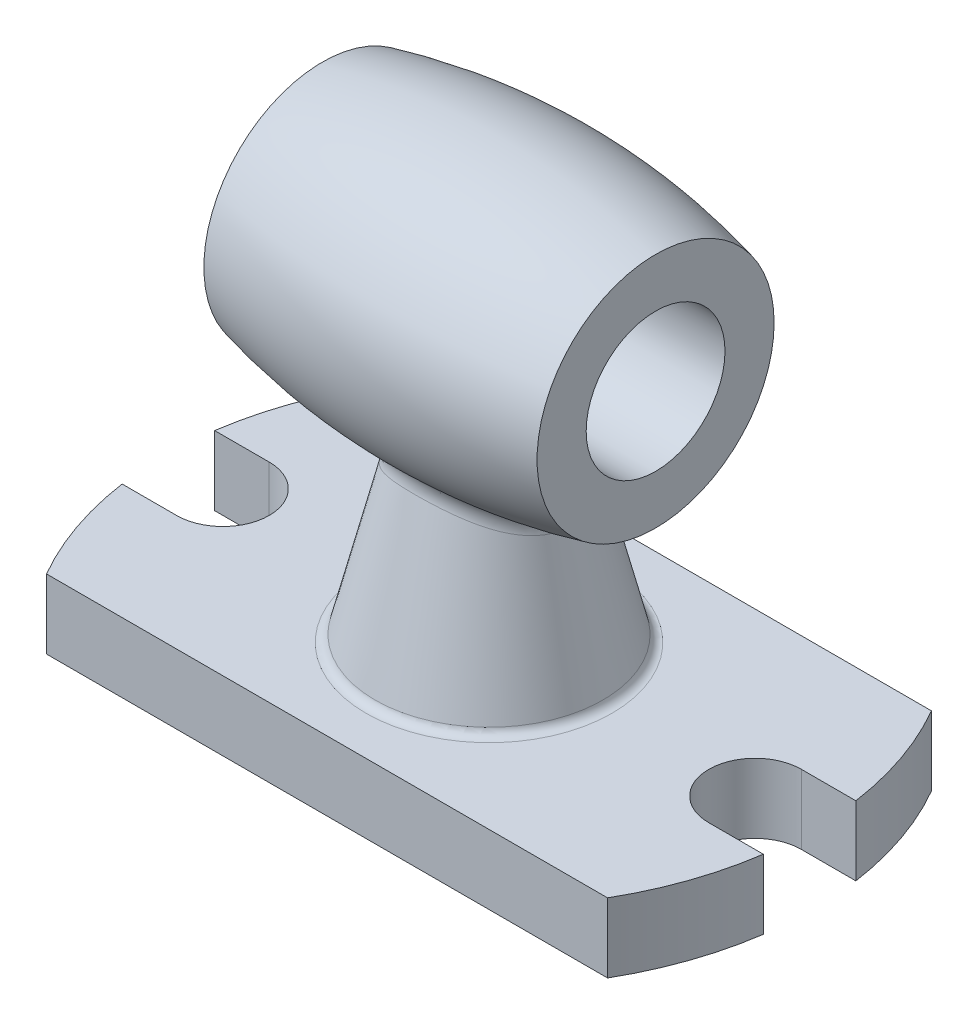
SolidWorks part; units mm, degrees
material "Plain Carbon Steel"
ref_plane "Front Plane" through (0, 0, 0) normal (0, 0, 1) x (1, 0, 0)
ref_plane "Top Plane" through (0, 0, 0) normal (0, 1, 0) x (1, 0, 0)
ref_plane "Right Plane" through (0, 0, 0) normal (1, 0, 0) x (0, 0, -1)
sketch "Sketch1" plane through (0, 0, 0) normal (0, 1, 0) x (1, 0, 0)
  line L0 (9.1225, -9.257) -> (9.1225, 60.743) construction
  line L5 (-48.3775, 60.743) -> (66.6225, 60.743)
  line L7 (-48.3775, -9.257) -> (66.6225, -9.257)
  line L9 (-48.3775, 25.743) -> (66.6225, 25.743) construction
  line L10 (66.6225, 60.743) -> (69.7443, 60.743)
  line L11 (66.6225, -9.257) -> (69.7443, -9.257)
  line L12 (-48.3775, 60.743) -> (-51.4993, 60.743)
  line L13 (-48.3775, -9.257) -> (-51.4993, -9.257)
  line L16 (-48.3775, 60.743) -> (-48.3775, -9.257) construction
  line L17 (66.6225, 60.743) -> (66.6225, -9.257) construction
  line L18 (-48.3775, 35.743) -> (-60.1596, 35.743)
  line L19 (-48.3775, 15.743) -> (-60.1596, 15.743)
  line L20 (66.6225, 35.743) -> (78.4045, 35.743)
  line L21 (66.6225, 15.743) -> (78.4045, 15.743)
  arc A0 (-51.4993, 60.743) -> (-60.1596, 35.743) centre (9.1225, 25.743) ccw
  arc A1 (69.7443, -9.257) -> (78.4045, 15.743) centre (9.1225, 25.743) ccw
  arc A2 (-48.3775, 15.743) -> (-48.3775, 35.743) centre (-48.3775, 25.743) ccw
  arc A3 (66.6225, 35.743) -> (66.6225, 15.743) centre (66.6225, 25.743) ccw
  arc A4 (78.4045, 35.743) -> (69.7443, 60.743) centre (9.1225, 25.743) ccw
  arc A5 (-60.1596, 15.743) -> (-51.4993, -9.257) centre (9.1225, 25.743) ccw
  dimension "D3" = 70
  dimension "D4" = 20
  dimension "D5" = 20
  dimension "D1" = 115
  dimension "D2" = 70
extrude "Boss-Extrude1" add sketch "Sketch1" along normal blind 15
ref_plane "Plane1" through (9.1225, 0, 0) normal (-1, 0, 0) x (0, 0, 1)
sketch "Sketch2" plane through (9.1225, 0, 0) normal (-1, 0, 0) x (0, 0, 1)
  line L0 (-25.743, 80) -> (-25.743, 15)
  line L1 (-15.743, 15) -> (-35.743, 15) construction
  line L2 (-50.743, 15) -> (-34.5367, 80)
  line L7 (-25.743, 15) -> (-50.743, 15)
  line L12 (-34.5367, 80) -> (-25.743, 80)
  dimension "D1" = 14
  dimension "D3" = 25
  dimension "D4" = 65
revolve "Revolve1" add sketch "Sketch2" angle 360 about L0
ref_plane "Plane2" through (0, 0, -25.743) normal (0, 0, 1) x (1, 0, 0)
sketch "Sketch6" plane through (0, 0, -25.743) normal (0, 0, 1) x (1, 0, 0)
  line L0 (-36.7283, 110) -> (-26.8775, 110) construction
  line L1 (-51.4993, 0) -> (69.7443, 0) construction
  line L2 (45.1225, 80) -> (60.6354, 80) construction
  line L3 (-41.3442, 95) -> (-26.8775, 95) construction
  line L4 (-60.1596, 15) -> (-60.1596, 65) construction
  line L5 (78.4045, 15) -> (78.4045, 83.7106) construction
  line L6 (-60.1596, 50) -> (-26.8775, 50) construction
  line L7 (9.1225, 50) -> (9.1225, 110) construction
  line L8 (9.1225, 50) -> (9.1225, -40) construction
  line L9 (45.1225, 80) -> (-26.8775, 80)
  line L10 (-43.3136, 65) -> (-26.8775, 65) construction
  line L11 (-26.8775, 119.2378) -> (-26.8775, 110) construction
  line L12 (45.1225, 119.2378) -> (45.1225, 110) construction
  line L13 (45.1225, 80) -> (45.1225, 105.6159)
  line L15 (45.1225, 110) -> (54.5117, 110) construction
  line L16 (45.1225, 95) -> (57.6813, 95) construction
  line L17 (45.1225, 65) -> (47.1571, 65) construction
  line L18 (45.1225, 50) -> (78.4045, 50) construction
  line L19 (-26.8775, 80) -> (-26.8775, 105.6159)
  line L20 (45.1225, 105.6159) -> (45.1225, 30.536) construction
  line L21 (-26.8775, 105.6159) -> (-26.8775, 34.2287) construction
  arc A0 (45.1225, 105.6159) -> (-26.8775, 105.6159) centre (9.1225, -40) ccw
  dimension "D9" = 150
  dimension "D1" = 110
  dimension "D2" = 30
  dimension "D3" = 15
  dimension "D4" = 36
  dimension "D5" = 36
  dimension "D6" = 15
  dimension "D7" = 15
  dimension "D8" = 150
revolve "Revolve2" add sketch "Sketch6" angle 360 about L9
sketch "Sketch9" plane through (-26.8775, 0, 0) normal (-1, 0, 0) x (0, 0, 1)
  circle A0 centre (-25.743, 80) radius 15
  dimension "D1" = 30
extrude "Cut-Extrude1" cut sketch "Sketch9" against normal through all
fillet "Fillet1" radius 5 1 edges at (19.6874, 52.6881, -14.2606)
fillet "Fillet2" radius 2 1 edges at (9.1225, 15, -0.743)
